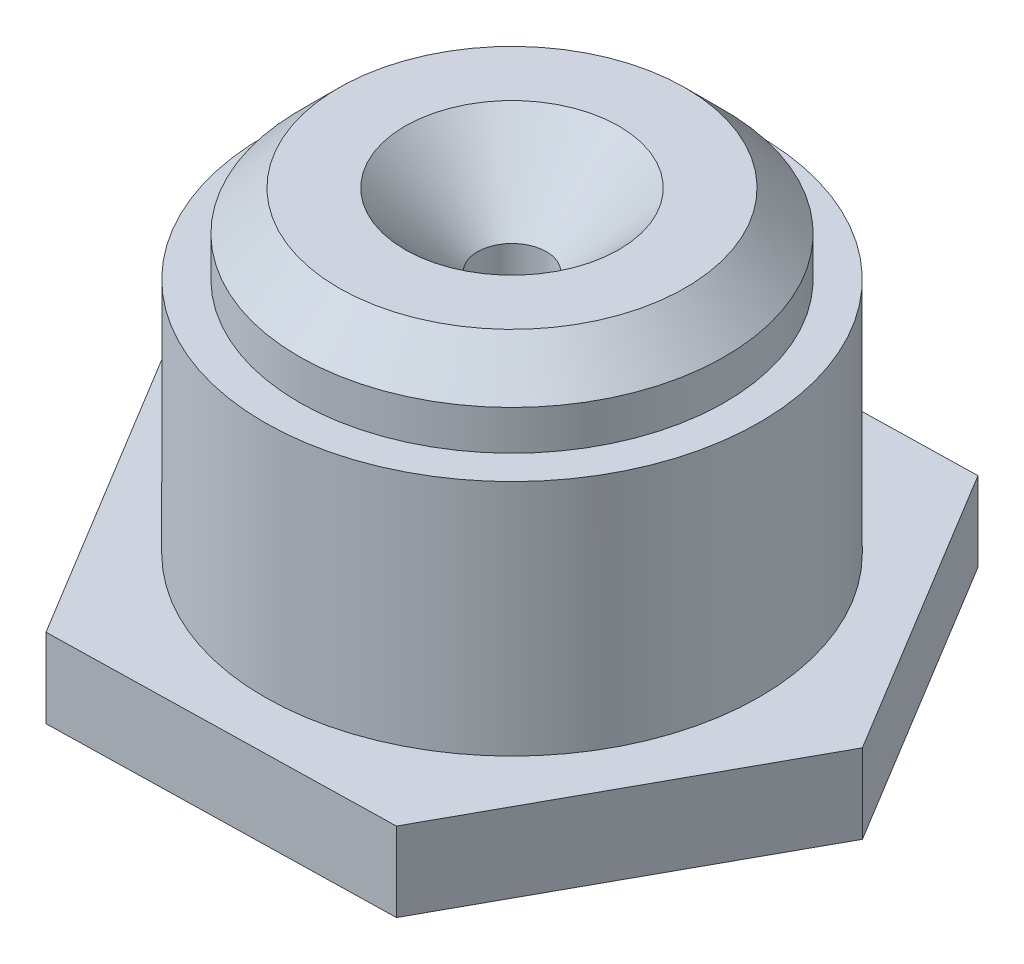
SolidWorks part; units mm, degrees
material "6061-T6 (SS)"
ref_plane "Front Plane" through (0, 0, 0) normal (0, 0, 1) x (1, 0, 0)
ref_plane "Top Plane" through (0, 0, 0) normal (0, 1, 0) x (1, 0, 0)
ref_plane "Right Plane" through (0, 0, 0) normal (1, 0, 0) x (0, 0, -1)
ref_axis "Axis1" through (0, 110.1512, 0) along (0, -1, 0)
sketch "Sketch1" plane through (0, 0, 0) normal (0, 0, 1) x (1, 0, 0)
  line L0 (-15.875, 15.24) -> (-13.6487, 15.24)
  line L1 (-15.875, 0) -> (-15.875, 15.24)
  line L2 (-13.6487, 15.24) -> (-13.6487, 20.32)
  line L3 (-13.6487, 20.32) -> (-6.858, 20.32)
  line L5 (-2.2098, 15.6718) -> (0, 15.6718)
  line L6 (-15.875, 0) -> (0, 0)
  line L8 (0, 110.1512) -> (0, -76.4241) construction
  line L9 (0, 15.6718) -> (0, 0)
  line L10 (-6.858, 20.32) -> (-2.2098, 15.6718)
  point P0 (-6.858, 28.1715)
  dimension "D1" = 15.875
  dimension "D2" = 15.24
  dimension "D3" = 135
  dimension "D4" = 6.858
  dimension "D5" = 13.6487
  dimension "D6" = 2.2098
  dimension "D7" = 5.08
revolve "Revolve1" add sketch "Sketch1" angle 360 about axis through (0, 110.1512, 0) along (0, -1, 0)
cosmetic thread "Cosmetic Thread1" parameters "D2"=27.4295
ref_plane "Plane2" through (0, 110.1512, 0) normal (-1, 0, 0) x (0, 0, 1)
sketch "Sketch12" plane through (0, 0, 0) normal (0, -1, 0) x (1, 0, 0)
  line L1 (-21.992, 0.4698) -> (-11.4029, -18.8107)
  line L2 (-11.4029, -18.8107) -> (10.5891, -19.2806)
  line L3 (10.5891, -19.2806) -> (21.992, -0.4698)
  line L4 (21.992, -0.4698) -> (11.4029, 18.8107)
  line L5 (11.4029, 18.8107) -> (-10.5891, 19.2806)
  line L6 (-10.5891, 19.2806) -> (-21.992, 0.4698)
  circle A0 centre (0, 0) radius 19.05 construction
  dimension "D1" = 38.1
extrude "Boss-Extrude2" add sketch "Sketch12" along normal blind 5.08
sketch "Sketch2" plane through (0, 15.6718, 0) normal (0, 1, 0) x (1, 0, 0)
  circle A0 centre (0, 0) radius 2.2098
extrude "Cut-Extrude2" cut sketch "Sketch2" against normal through all
ref_plane "Plane4" through (0, 110.1512, 0) normal (-1, 0, 0) x (0, 0, 1)
ref_plane "Plane6" through (0, 110.1512, 0) normal (-1, 0, 0) x (0, 0, 1)
chamfer "Chamfer2" distance 2.54 angle 45 1 edges at (0, 20.32, 13.6487)
